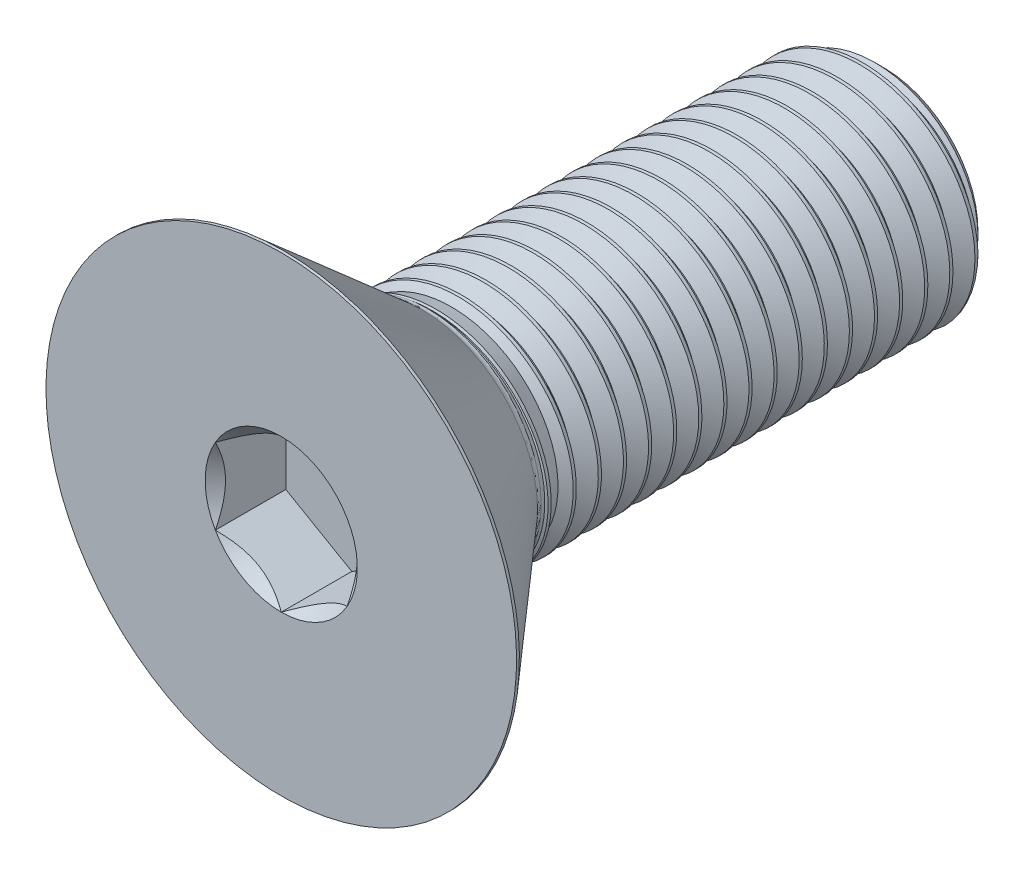
SolidWorks part; units mm, degrees
ref_plane "Front Plane" through (0, 0, 0) normal (0, 0, 1) x (1, 0, 0)
ref_plane "Top Plane" through (0, 0, 0) normal (0, 1, 0) x (1, 0, 0)
ref_plane "Right Plane" through (0, 0, 0) normal (1, 0, 0) x (0, 0, -1)
sketch "Sketch1" plane through (0, 0, 0) normal (1, 0, 0) x (0, 0, -1)
  line L0 (-12.7, 0) -> (12.7, 0) construction
  line L1 (-12.7, 0) -> (-12.7, 9.9187)
  line L2 (-12.7, 9.9187) -> (-12.5811, 9.9187)
  line L3 (-12.5811, 9.9187) -> (-6.7564, 4.8553)
  line L4 (-12.5811, -9.9187) -> (-6.7564, -4.8553)
  line L5 (12.7, 0) -> (12.7, 4.7625)
  line L6 (12.7, 4.7625) -> (-6.7564, 4.7625)
  line L7 (11.9062, 4.7625) -> (12.7, 3.9687)
  line L8 (12.6339, 4.8771) -> (13.163, 3.9605) construction
  line L9 (13.163, 3.9605) -> (13.6922, 4.8771) construction
  line L10 (13.6922, 4.8771) -> (12.6339, 4.8771) construction
  line L11 (12.6669, 4.8198) -> (13.6591, 4.8198)
  line L12 (13.6591, 4.8198) -> (13.2292, 4.0751)
  line L13 (13.2292, 4.0751) -> (13.0969, 4.0751)
  line L14 (13.0969, 4.0751) -> (12.6669, 4.8198)
  line L15 (13.163, 4.0751) -> (13.163, 3.9605) construction
  line L16 (12.7, 4.7625) -> (13.626, 4.7625) construction
  line L17 (13.163, 4.8771) -> (13.163, 4.7625) construction
  line L18 (12.7, -4.7625) -> (-6.7564, -4.7625)
  arc A0 (-6.7564, 4.8553) -> (-6.5081, 4.7625) centre (-6.5081, 5.141) ccw
  point P2 (0, 0)
  point P23 (-9.7282, 0)
  point P27 (13.163, 4.8198)
  point P30 (11.1125, -4.7625)
  point P31 (-6.7564, 9.9187)
  point P34 (-12.5811, -9.9187)
  dimension "Length" = 25.4
  dimension "Head Height" = 5.9436
  dimension "Head Diameter" = 19.8374
  dimension "Countersink Angle" = 82
  dimension "Screw Size Decimal Equivalent" = 9.525
  dimension "Pitch" = 1.0583
  dimension "D4" = 0.1323
  dimension "D3" = 45
  dimension "D5" = 0.7938
  dimension "D6" = 2.9718
  dimension "D1" = 1.5875
  dimension "D7" = 0.1189
sketch "Sketch8" plane through (0, 0, 0) normal (0, 0, 1) x (1, 0, 0)
  line L1 (0, 3.2079) -> (-2.7781, 1.604)
  line L2 (-2.7781, 1.604) -> (-2.7781, -1.604)
  line L3 (-2.7781, -1.604) -> (0, -3.2079)
  line L4 (0, -3.2079) -> (2.7781, -1.604)
  line L5 (2.7781, -1.604) -> (2.7781, 1.604)
  line L6 (2.7781, 1.604) -> (0, 3.2079)
  circle A0 centre (0, 0) radius 2.7781 construction
  dimension "Drive Size" = 5.5562
sketch "Sketch2" plane through (0, 0, 0) normal (1, 0, 0) x (0, 0, -1)
  line L0 (-12.5811, 9.9187) -> (-6.7564, 4.8553) construction
  line L1 (-12.7, 0) -> (-12.7, 9.9187) construction
  line L2 (-12.5811, 9.9187) -> (-6.7564, 4.8553)
  line L3 (-12.7, 0) -> (-12.7, 9.9187)
  line L4 (-12.7, 9.9187) -> (-12.5811, 9.9187) construction
  line L5 (-12.7, 9.9187) -> (-12.5811, 9.9187)
  line L6 (-6.5081, 4.7625) -> (11.9062, 4.7625)
  line L7 (11.9062, 4.7625) -> (12.7, 3.9687)
  line L8 (12.7, 3.9687) -> (12.7, 0)
  line L9 (12.7, 0) -> (-12.7, 0)
  arc A0 (-6.7564, 4.8553) -> (-6.5081, 4.7625) centre (-6.5081, 5.141) ccw construction
  arc A1 (-6.7564, 4.8553) -> (-6.5081, 4.7625) centre (-6.5081, 5.141) ccw
revolve "Revolve1" add sketch "Sketch2" angle 360 about L9
sketch "Sketch9" plane through (0, 0, 12.7) normal (0, 0, 1) x (1, 0, 0)
  line L0 (2.7781, -1.604) -> (2.7781, 1.604) construction
  line L1 (0, -3.2079) -> (2.7781, -1.604) construction
  line L2 (-2.7781, -1.604) -> (0, -3.2079) construction
  line L3 (-2.7781, 1.604) -> (-2.7781, -1.604) construction
  line L4 (0, 3.2079) -> (-2.7781, 1.604) construction
  line L5 (2.7781, 1.604) -> (0, 3.2079) construction
  line L6 (2.7781, -1.604) -> (2.7781, 1.604)
  line L7 (0, -3.2079) -> (2.7781, -1.604)
  line L8 (-2.7781, -1.604) -> (0, -3.2079)
  line L9 (-2.7781, 1.604) -> (-2.7781, -1.604)
  line L10 (0, 3.2079) -> (-2.7781, 1.604)
  line L11 (2.7781, 1.604) -> (0, 3.2079)
sketch "Sketch10" plane through (0, 0, 12.7) normal (0, 0, 1) x (1, 0, 0)
  circle A0 centre (0, 0) radius 3.2079
extrude "Cut-Extrude2" cut sketch "Sketch10" against normal up to vertex (2.9718 mm away) draft 45 up to point (0, 0, 9.7282)
extrude "Cut-Extrude1" cut sketch "Sketch9" against normal up to vertex (2.9718 mm away) up to point (0, 0, 9.7282)
ref_plane "Plane1" through (0, 0, 6.5081) normal (0, 0, 1) x (1, 0, 0)
split "Split1" trim tools "Plane1" bodies to split 111 resulting bodies 105 106
sketch "Sketch3" plane through (0, 0, -12.7) normal (0, 0, -1) x (-1, 0, 0)
  circle A0 centre (0, 0) radius 4.7625 construction
  circle A1 centre (0, 0) radius 4.7625
curve "Helix/Spiral1" pitch 1.0583 height 25.4 turns 24
sketch "Sketch4" plane through (0, 0, 0) normal (1, 0, 0) x (0, 0, -1)
  line L0 (12.6669, 4.8198) -> (13.6591, 4.8198) construction
  line L1 (13.0969, 4.0751) -> (12.6669, 4.8198) construction
  line L2 (13.2292, 4.0751) -> (13.0969, 4.0751) construction
  line L3 (13.6591, 4.8198) -> (13.2292, 4.0751) construction
  line L4 (12.6669, 4.8198) -> (13.6591, 4.8198)
  line L5 (13.0969, 4.0751) -> (12.6669, 4.8198)
  line L6 (13.2292, 4.0751) -> (13.0969, 4.0751)
  line L7 (13.6591, 4.8198) -> (13.2292, 4.0751)
sweep "Cut-Sweep1" cut profiles "Sketch4" path "Helix/Spiral1"
sketch "Sketch7" plane through (0, 0, 6.5081) normal (0, 0, 1) x (1, 0, 0)
  circle A0 centre (0, 0) radius 4.7625
extrude "Boss-Extrude2" add sketch "Sketch7" against normal up to next (19.2081 mm away) draft 20
equation "\"D4@Sketch1\" = \"Pitch@Sketch1\" / 8"
equation "\"D5@Sketch1\"=\"Pitch@Sketch1\"*0.75"
equation "\"D4@Helix/Spiral1\"=\"Pitch@Sketch1\""
equation "\"D3@Helix/Spiral1\"=\"Length@Sketch1\""
equation "\"D6@Sketch1\"=\"Head Height@Sketch1\"/2"
equation "\"D1@Sketch1\"=\"Pitch@Sketch1\"*1.5"
equation "\"D7@Sketch1\"=\"Head Height@Sketch1\"*0.02"
